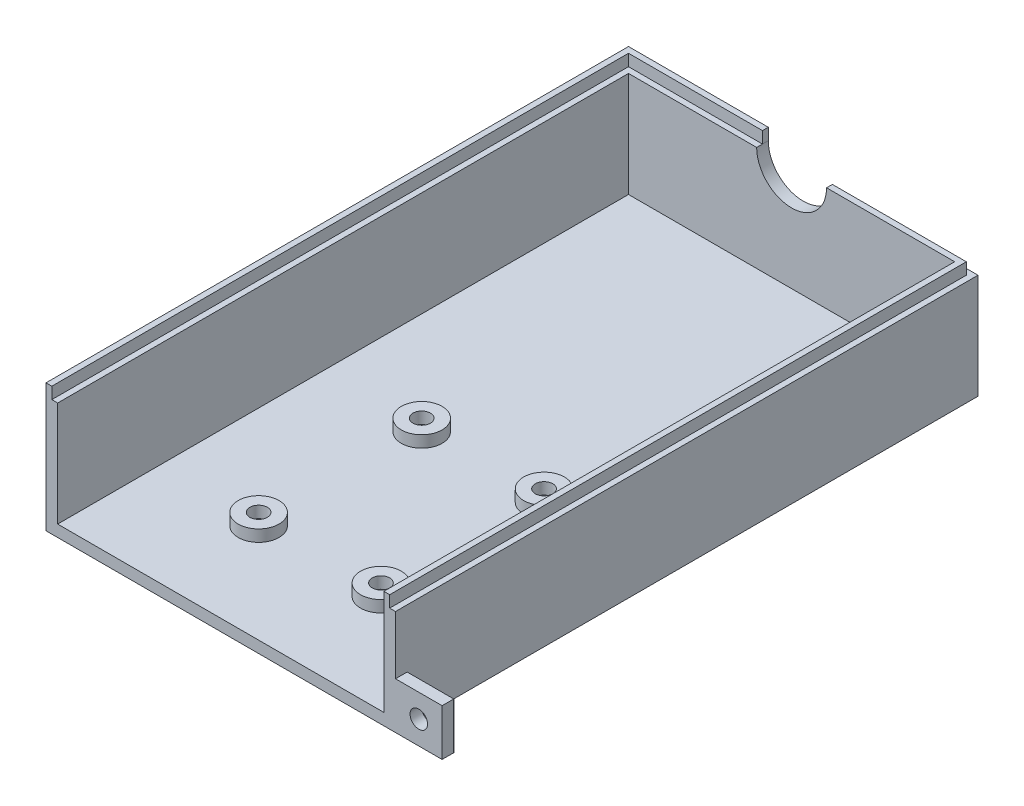
SolidWorks part; units mm, degrees
ref_plane "Front Plane" through (0, 0, 0) normal (0, 0, 1) x (1, 0, 0)
ref_plane "Top Plane" through (0, 0, 0) normal (0, 1, 0) x (1, 0, 0)
ref_plane "Right Plane" through (0, 0, 0) normal (1, 0, 0) x (0, 0, -1)
sketch "Sketch3" plane through (0, 0, 0) normal (0, 1, 0) x (1, 0, 0)
  line L1 (0, 0) -> (60, 0)
  line L2 (0, 0) -> (0, 100)
  line L3 (0, 100) -> (60, 100)
  line L4 (60, 0) -> (60, 100)
  dimension "D1" = 100
  dimension "D2" = 60
extrude "Boss-Extrude1" add sketch "Sketch3" along normal blind 40
shell "Shell1" thickness 2 removed face at (30, 20, 0)
sketch "Sketch2" plane through (0, 2, 0) normal (0, 1, 0) x (1, 0, 0)
  line L0 (19.5, 17) -> (19.5, 45) construction
  line L1 (12.5, 10) -> (47.5, 10)
  line L2 (12.5, 10) -> (12.5, 52)
  line L3 (12.5, 52) -> (47.5, 52)
  line L4 (47.5, 10) -> (47.5, 52)
  line L5 (19.5, 45) -> (40.5, 45) construction
  line L6 (40.5, 17) -> (40.5, 45) construction
  line L7 (19.5, 17) -> (40.5, 17) construction
  line L12 (30, 0) -> (30, 100) construction
  line L13 (0, 0) -> (60, 0) construction
  line L14 (60, 100) -> (0, 100) construction
  line L15 (0, 31) -> (60, 31) construction
  line L16 (0, 100) -> (0, 0) construction
  line L17 (60, 0) -> (60, 100) construction
  line L18 (12.5, 52) -> (0, 52)
  line L19 (0, 52) -> (0, 10)
  line L20 (0, 10) -> (60, 10)
  line L21 (60, 10) -> (60, 52)
  line L22 (60, 52) -> (47.5, 52)
  line L23 (0, 52) -> (0, 100)
  line L24 (0, 100) -> (60, 100)
  line L25 (60, 100) -> (60, 52)
  circle A0 centre (19.5, 45) radius 1.5
  circle A1 centre (40.5, 45) radius 1.5
  circle A2 centre (40.5, 17) radius 1.5
  circle A3 centre (19.5, 17) radius 1.5
  circle A4 centre (19.5, 45) radius 3.5
  circle A5 centre (40.5, 45) radius 3.5
  circle A6 centre (40.5, 17) radius 3.5
  circle A7 centre (19.5, 17) radius 3.5
  point P1 (30, 10)
  point P20 (12.5, 31)
  dimension "D4" = 3
  dimension "D5" = 7
  dimension "D1" = 42
  dimension "D2" = 10
  dimension "D3" = 7
extrude "Boss-Extrude2" add sketch "Sketch2" along normal blind 2 contours A7 A3 | A6 A2 | A5 A1 | A4 A0 region at (16.099, 2, -45) region at (37.099, 2, -45) region at (37.099, 2, -17) region at (16.099, 2, -17)
ref_plane "Plane1" through (0, 20, 0) normal (0, 1, 0) x (1, 0, 0)
sketch "Sketch4" plane through (0, 20, 0) normal (0, 1, 0) x (1, 0, 0)
  line L1 (0, 0) -> (60, 0)
  line L2 (0, 0) -> (0, 100)
  line L3 (0, 100) -> (60, 100)
  line L4 (60, 0) -> (60, 100)
extrude "Cut-Extrude1" cut sketch "Sketch4" along normal up to next
sketch "Sketch5" plane through (0, 0, -98) normal (0, 0, 1) x (1, 0, 0)
  line L0 (30, 0) -> (30, 20) construction
  line L1 (0, 0) -> (60, 0) construction
  line L2 (33, 20) -> (-33, 20) construction
  circle A0 centre (30, 20) radius 6
  dimension "D1" = 12
extrude "Cut-Extrude2" cut sketch "Sketch5" against normal up to next
sketch "Sketch6" plane through (0, 20, 0) normal (0, 1, 0) x (1, 0, 0)
  line L0 (30, 100) -> (30, 99)
  line L2 (30, 99) -> (59, 99)
  line L3 (59, 99) -> (59, 0)
  line L4 (58, 0) -> (60, 0) construction
  line L5 (59, 0) -> (60, 0)
  line L6 (60, 0) -> (60, 100)
  line L7 (60, 100) -> (30, 100)
  line L8 (30, 100) -> (30, 0) construction
  line L9 (36, 100) -> (24, 100) construction
  line L10 (2, 0) -> (58, 0) construction
  line L11 (30, 100) -> (30, 99)
  line L12 (0, 100) -> (30, 100)
  line L13 (30, 99) -> (1, 99)
  line L14 (1, 0) -> (0, 0)
  line L15 (0, 0) -> (0, 100)
  line L16 (1, 99) -> (1, 0)
  line L17 (36, 100) -> (36, 99)
  line L18 (36, 98) -> (36, 100) construction
  line L19 (24, 100) -> (24, 99)
  line L20 (24, 100) -> (24, 98) construction
  line M8 (60, 100) -> (36, 100)
  line M9 (36, 100) -> (36, 98)
  line M12 (58, 0) -> (60, 0)
  line M13 (60, 0) -> (60, 100)
extrude "Cut-Extrude3" cut sketch "Sketch6" against normal blind 2 contours L2 L3 M12 M13 M8 M9 | L7 L0 L2 M9 region at (33, 20, -99.5) region at (48, 20, -99.8972)
extrude "Boss-Extrude3" add sketch "Sketch6<3>" along normal blind 2 contours L16 L13 L11 L12 L15 L14 region at (22.9716, 20, -99.5)
sketch "Sketch6<3>" plane through (0, 20, 0) normal (0, 1, 0) x (1, 0, 0) same geometry as "Sketch6"
sketch "Sketch7" plane through (0, 0, 0) normal (0, 0, 1) x (1, 0, 0)
  line L0 (60, 4) -> (68, 4) construction
  line L1 (60, 0) -> (68, 0)
  line L2 (60, 0) -> (60, 8)
  line L3 (60, 8) -> (68, 8)
  line L4 (68, 0) -> (68, 8)
  circle A0 centre (64, 4) radius 1.5
  dimension "D2" = 3
  dimension "D1" = 8
extrude "Boss-Extrude4" add sketch "Sketch7" against normal blind 2
